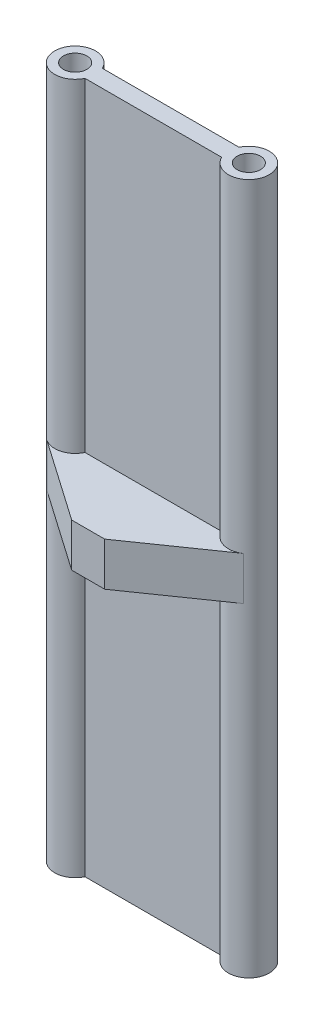
SolidWorks part; units mm, degrees
ref_plane "Front Plane" through (0, 0, 0) normal (0, 0, 1) x (1, 0, 0)
ref_plane "Top Plane" through (0, 0, 0) normal (0, 1, 0) x (1, 0, 0)
ref_plane "Right Plane" through (0, 0, 0) normal (1, 0, 0) x (0, 0, -1)
sketch "Sketch1" plane through (0, 0, 0) normal (0, 1, 0) x (1, 0, 0)
  line L0 (25.4, 0) -> (-25.4, 0) construction
  line L1 (19.9984, 2.54) -> (-19.9984, 2.54)
  line L2 (19.9984, -2.54) -> (-19.9984, -2.54)
  line L3 (0, 2.54) -> (0, -2.54) construction
  circle A0 centre (-25.4, 0) radius 3.429
  circle A1 centre (25.4, 0) radius 3.429
  arc A2 (-19.9984, 2.54) -> (-19.9984, -2.54) centre (-25.4, 0) ccw
  arc A3 (19.9984, -2.54) -> (19.9984, 2.54) centre (25.4, 0) ccw
  circle A4 centre (-25.4, 0) radius 5.969 construction
  circle A5 centre (25.4, 0) radius 5.969 construction
  point P4 (0, 0)
  point P16 (0, 0)
  dimension "D2" = 6.858
  dimension "D3" = 6.858
  dimension "D1" = 50.8
  dimension "D5" = 5.08
  dimension "D4" = 2.54
extrude "Boss-Extrude1" add sketch "Sketch1" along normal blind 202.2602
ref_plane "Midplane" through (0, 101.1301, 0) normal (0, 1, 0) x (1, 0, 0)
sketch "ID of Airframe Coupler" plane through (0, 0, 0) normal (0, 1, 0) x (1, 0, 0)
  circle A0 centre (0, 0) radius 36.5125
  dimension "D1" = 73.025
sketch "Sketch3" plane through (0, 101.1301, 0) normal (0, 1, 0) x (1, 0, 0)
  line L0 (-28.8096, 4.8994) -> (-4.826, 21.59)
  line L1 (28.8096, 4.8994) -> (4.826, 21.59)
  line L2 (-4.826, 21.59) -> (4.826, 21.59)
  line L3 (19.9984, 2.54) -> (-19.9984, 2.54) construction
  line L5 (19.9984, 2.54) -> (-19.9984, 2.54)
  line L6 (-19.9984, -2.54) -> (19.9984, -2.54)
  line L7 (19.9984, 2.54) -> (-19.9984, 2.54)
  arc A2 (19.9984, -2.54) -> (19.9984, 2.54) centre (25.4, 0) ccw
  arc A3 (-19.9984, 2.54) -> (-19.9984, -2.54) centre (-25.4, 0) ccw
  arc A4 (28.8096, 4.8994) -> (19.9984, 2.54) centre (25.4, 0) ccw
  arc A5 (-19.9984, 2.54) -> (-28.8096, 4.8994) centre (-25.4, 0) ccw
  point P4 (0, 21.59)
  point P5 (-25.4, 5.969)
  point P11 (-32.9367, 2.54)
  point P16 (34.9135, 1.4572)
  point P17 (-28.4919, 5.1058)
  dimension "D2" = 19.05
  dimension "D3" = 9.652
  dimension "D1" = 0
extrude "Boss-Extrude2" add sketch "Sketch3" along normal mid plane 12.7
ref_axis "Axis1" through (0, -10.113, 0) along (0, 1, 0)
pattern_circular "CirPattern1" count 2 over 360 about axis through (0, -10.113, 0) along (0, 1, 0) of "Boss-Extrude2"
equation "\"D3@Sketch1\"=\"D2@Sketch1\""
